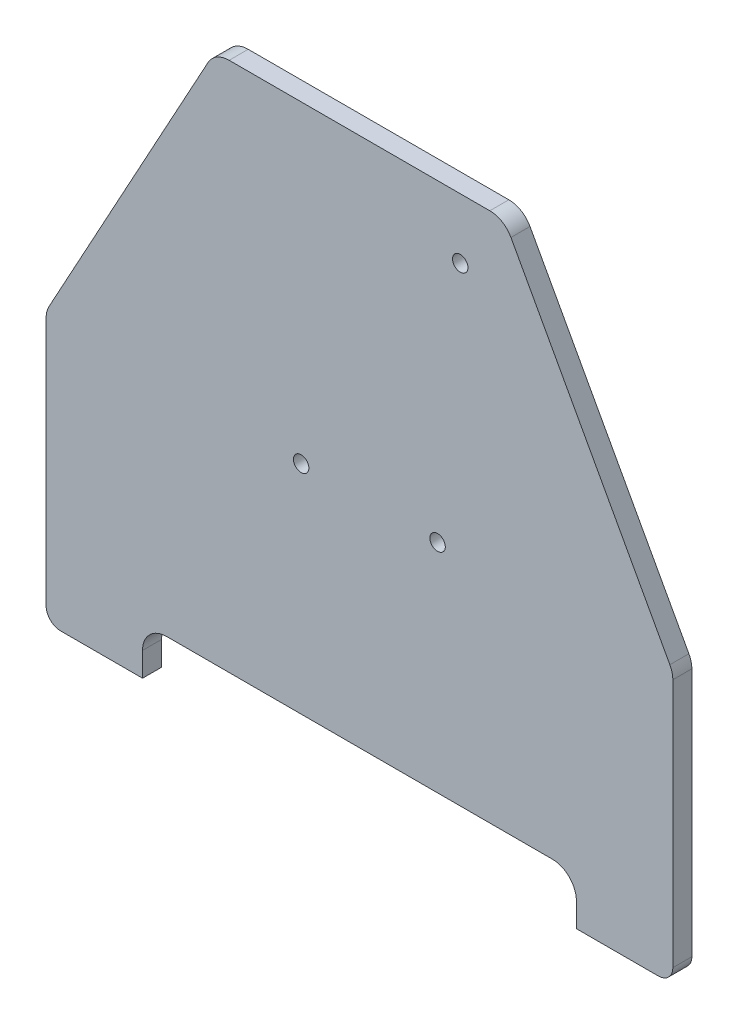
SolidWorks part; units mm, degrees
ref_plane "Front Plane" through (0, 0, 0) normal (0, 0, 1) x (1, 0, 0)
ref_plane "Top Plane" through (0, 0, 0) normal (0, 1, 0) x (1, 0, 0)
ref_plane "Right Plane" through (0, 0, 0) normal (1, 0, 0) x (0, 0, -1)
sketch "Sketch1" plane through (0, 0, 0) normal (0, 0, 1) x (1, 0, 0)
  line L0 (0, 56) -> (35, 120)
  line L2 (0, 56) -> (0, 0)
  line L3 (0, 0) -> (20, 0)
  line L4 (130, 56) -> (130, 0)
  line L8 (20, 0) -> (20, 10)
  line L9 (20, 10) -> (110, 10)
  line L10 (110, 0) -> (110, 10)
  line L11 (35, 120) -> (95, 120)
  line L12 (95, 120) -> (130, 56)
  line L13 (110, 0) -> (130, 0)
  point P0 (0, 0)
  dimension "D1" = 130
  dimension "D2" = 20
  dimension "D3" = 56
  dimension "D4" = 60
  dimension "D5" = 10
  dimension "D6" = 120
extrude "Boss-Extrude2" add sketch "Sketch1" along normal blind 3.95
fillet "Fillet1" radius 5 6 edges at (130, 56, 1.975) (95, 120, 1.975) (35, 120, 1.975) (0, 56, 1.975) (110, 10, 1.975) (20, 10, 1.975)
fillet "Fillet2" radius 3 2 edges at (130, 0, 1.975) (0, 0, 1.975)
sketch "Sketch2" plane through (0, 0, 3.95) normal (0, 0, 1) x (1, 0, 0)
  line L0 (25, 10) -> (105, 10) construction
  line L1 (92.0355, 120) -> (37.9645, 120) construction
  line L2 (35, 120) -> (95, 120) construction
  line L3 (35, 120) -> (35, 10) construction
  line L4 (35, 10) -> (95, 10) construction
  line L5 (95, 120) -> (95, 10) construction
  circle A0 centre (81.2035, 55) radius 1.6
  circle A1 centre (85.9, 107.4903) radius 1.6
  circle A2 centre (52.9035, 55) radius 1.6
  point P13 (65, 120)
  point P16 (65, 120)
  dimension "D1" = 3.2
  dimension "D6" = 62
  dimension "D2" = 45
  dimension "D3" = 28.3
  dimension "D4" = 52.7
  dimension "D5" = 60
  dimension "D7" = 110
  dimension "D8" = 50.9
extrude "Cut-Extrude1" cut sketch "Sketch2" against normal through all
